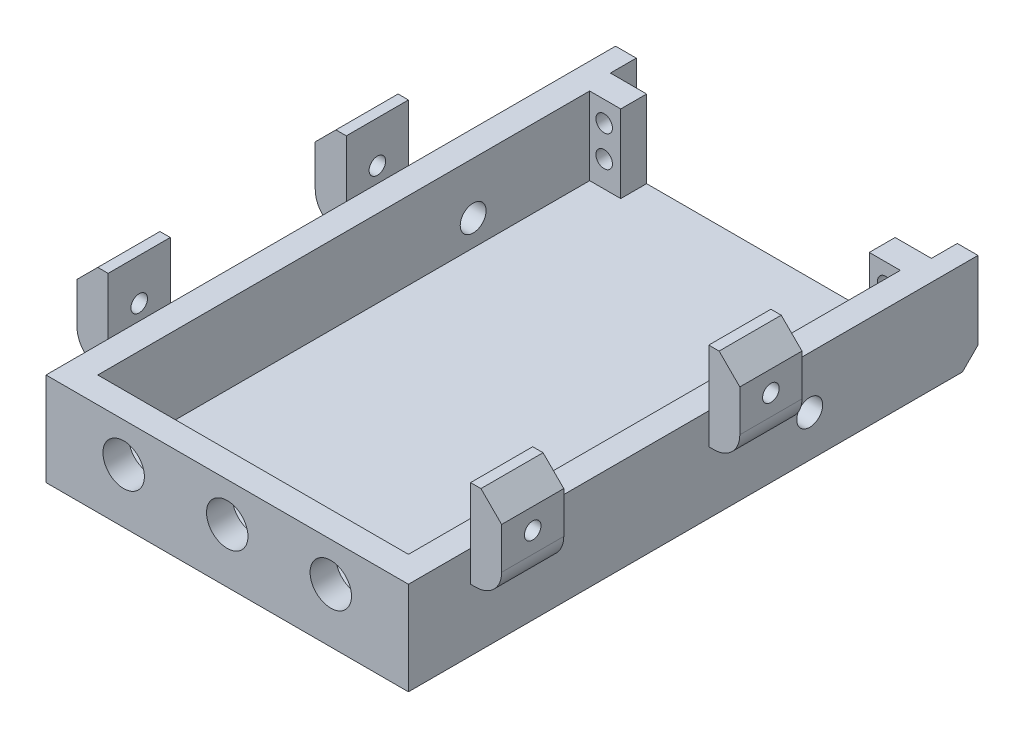
SolidWorks part; units mm, degrees
ref_plane "Alzado" through (0, 0, 0) normal (0, 0, 1) x (1, 0, 0)
ref_plane "Planta" through (0, 0, 0) normal (0, 1, 0) x (1, 0, 0)
ref_plane "Vista lateral" through (0, 0, 0) normal (1, 0, 0) x (0, 0, -1)
sketch "Croquis1" plane through (0, 0, 0) normal (0, 1, 0) x (1, 0, 0)
  line L1 (-35, 52.5) -> (35, 52.5)
  line L2 (-35, 52.5) -> (-35, -52.5)
  line L3 (-35, -52.5) -> (35, -52.5)
  line L4 (35, 52.5) -> (35, -52.5)
  line L5 (-35, 52.5) -> (35, -52.5) construction
  line L6 (-35, -52.5) -> (35, 52.5) construction
  point P0 (0, 0)
  dimension "D1" = 105
  dimension "D2" = 70
extrude "Saliente-Extruir1" add sketch "Croquis1" along normal blind 3
sketch "Croquis2" plane through (0, 3, 0) normal (0, 1, 0) x (1, 0, 0)
  line L1 (-35, 52.5) -> (-30, 52.5)
  line L2 (-35, 52.5) -> (-35, -52.5)
  line L4 (-30, 52.5) -> (-30, -47.5)
  line L5 (35, 52.5) -> (-35, 52.5) construction
  line L7 (35, -52.5) -> (35, 52.5)
  line L8 (35, 52.5) -> (30, 52.5)
  line L9 (30, -47.5) -> (30, 52.5)
  line L10 (-35, -52.5) -> (35, -52.5)
  line L12 (-30, -47.5) -> (30, -47.5)
  dimension "D1" = 5
  dimension "D2" = 5
  dimension "D3" = 100
  dimension "D4" = 100
extrude "Saliente-Extruir2" add sketch "Croquis2" along normal blind 15
ref_plane "Plano1" through (0, 0, -46.5) normal (0, 0, -1) x (-1, 0, 0)
sketch "Croquis10" plane through (35, 0, 0) normal (1, 0, 0) x (0, 0, -1)
  line L0 (11.5, 29) -> (11.5, 12) construction
  line L5 (-31.5, 18) -> (8.5, 18) construction
  line L10 (55, 0) -> (-55, 0) construction
  line L15 (8.5, 12) -> (17.5, 12)
  line L16 (8.5, 12) -> (8.5, 29)
  line L17 (8.5, 29) -> (17.5, 29)
  line L18 (17.5, 12) -> (17.5, 29)
  line L19 (-34.5, 12) -> (-28.5, 12)
  line L20 (11.5, 12) -> (5.5, 12)
  line L22 (11.5, 29) -> (5.5, 29)
  line L23 (5.5, 12) -> (5.5, 29)
  line L24 (-31.5, 12) -> (-40.5, 12)
  line L25 (-11.5, 11.4546) -> (-11.5, 24.5454)
  line L26 (52.5, 18) -> (52.5, 0) construction
  line L27 (-52.5, 18) -> (-52.5, 0) construction
  line L28 (-52.5, 0) -> (52.5, 0) construction
  line L29 (-40.5, 12) -> (-40.5, 29)
  line L30 (-34.5, 29) -> (-28.5, 29)
  line L31 (-31.5, 29) -> (-40.5, 29)
  line L32 (-28.5, 12) -> (-28.5, 29)
  circle A1 centre (11.5, 21) radius 1.6
  circle A2 centre (-34.5, 21) radius 1.6
  point P25 (-11.5, 18)
  line M7 (52.5, 18) -> (-52.5, 18)
  dimension "D10" = 3.2
  dimension "D8" = 9
  dimension "D4" = 8
  dimension "D2" = 12
  dimension "D3" = 35
  dimension "D5" = 12
  dimension "D6" = 21
  dimension "D7" = 18
  dimension "D14" = 3
  dimension "D15" = 6
extrude "Saliente-Extruir4" add sketch "Croquis10" along normal blind 6 contours L18 L17 L16 A1 M7 | L15 L18 L16 M7 | L23 L20 L16 M7 | L23 L16 L22 M7 | L32 L30 L31 L29 A2 M7 | L19 L32 L29 L24 M7 region at (35, 15, -13) region at (35, 15, -7) region at (35, 15, 34.5) region at (35, 23.6622, 34.5) region at (35, 23.5, -7) region at (35, 23.7211, -13.1326)
fillet "Redondeo1" radius 5 2 edges at (41, 12, -11.5) (41, 12, 34.5)
mirror "Simetría1" about plane through (0, 0, 0) normal (1, 0, 0) of "Saliente-Extruir4", "Redondeo1"
sketch "Croquis12" plane through (-30, 0, 0) normal (1, 0, 0) x (0, 0, -1)
  line L0 (-47.5, 18) -> (52.5, 18) construction
  line L1 (47.5, 18) -> (52.5, 18)
  line L2 (47.5, 18) -> (47.5, 3)
  line L3 (47.5, 3) -> (52.5, 3)
  line L4 (52.5, 18) -> (52.5, 3)
  dimension "D1" = 5
extrude "Saliente-Extruir5" add sketch "Croquis12" along normal blind 6
mirror "Simetría2" about plane through (0, 0, 0) normal (1, 0, 0) of "Saliente-Extruir5"
sketch "Croquis13" plane through (0, 0, 52.5) normal (0, 0, 1) x (1, 0, 0)
  line L0 (-35, 0) -> (35, 0) construction
  line L2 (0, 10.5) -> (20, 10.5) construction
  line L3 (0, 10.5) -> (-20, 10.5) construction
  line L4 (0, 0) -> (0, 10.5) construction
  circle A0 centre (-20, 10.5) radius 4
  circle A1 centre (0, 10.5) radius 4
  circle A2 centre (20, 10.5) radius 4
  dimension "D1" = 8
  dimension "D2" = 8
  dimension "D3" = 8
  dimension "D4" = 10.5
  dimension "D5" = 20
  dimension "D6" = 20
extrude "Cortar-Extruir1" cut sketch "Croquis13" against normal up to next
sketch "Croquis14" plane through (0, 0, -52.5) normal (0, 0, -1) x (-1, 0, 0)
  line L0 (27.2, 14) -> (27.2, 8) construction
  line L2 (24, 18) -> (35, 18) construction
  line L3 (24, 3) -> (24, 18) construction
  circle A0 centre (27.2, 14) radius 1.6
  circle A1 centre (27.2, 8) radius 1.6
  dimension "D1" = 3.2
  dimension "D2" = 3.2
  dimension "D3" = 6
  dimension "D4" = 4
  dimension "D5" = 3.2
extrude "Cortar-Extruir2" cut sketch "Croquis14" against normal up to next
mirror "Simetría3" about plane through (0, 0, 0) normal (1, 0, 0) of "Cortar-Extruir2"
sketch "Croquis15" plane through (0, 0, -52.5) normal (0, 0, -1) x (-1, 0, 0)
  line L0 (-27.2, 14) -> (27.2, 14) construction
sketch "Croquis16" plane through (-35, 0, 0) normal (-1, 0, 0) x (0, 0, 1)
  line L0 (0, 0) -> (0, 8) construction
  line L1 (-52.5, 0) -> (52.5, 0) construction
  line L2 (0, 8) -> (-25, 8) construction
  circle A0 centre (-25, 8) radius 2.5
  dimension "D1" = 5
  dimension "D2" = 8
  dimension "D3" = 25
extrude "Cortar-Extruir3" cut sketch "Croquis16" against normal blind 70
sketch "Croquis17" plane through (0, 0, 0) normal (0, 1, 0) x (1, 0, 0)
  line L1 (35, 52.5) -> (31, 52.5)
  line L2 (35, 52.5) -> (35, 57.5)
  line L3 (35, 57.5) -> (31, 57.5)
  line L4 (31, 52.5) -> (31, 57.5)
extrude "Saliente-Extruir6" add sketch "Croquis17" along normal up to surface (18 mm away) up to face at (0, 18, -5.4)
mirror "Simetría4" about plane through (0, 0, 0) normal (1, 0, 0) of "Saliente-Extruir6"
chamfer "Chaflán1" distance 3 angle 45 2 edges at (-33, 0, -57.5) (33, 0, -57.5)
chamfer "Chaflán2" distance 4 angle 45 4 edges at (41, 29, -11.5) (41, 29, 34.5) (-41, 29, -11.5) (-41, 29, 34.5)
